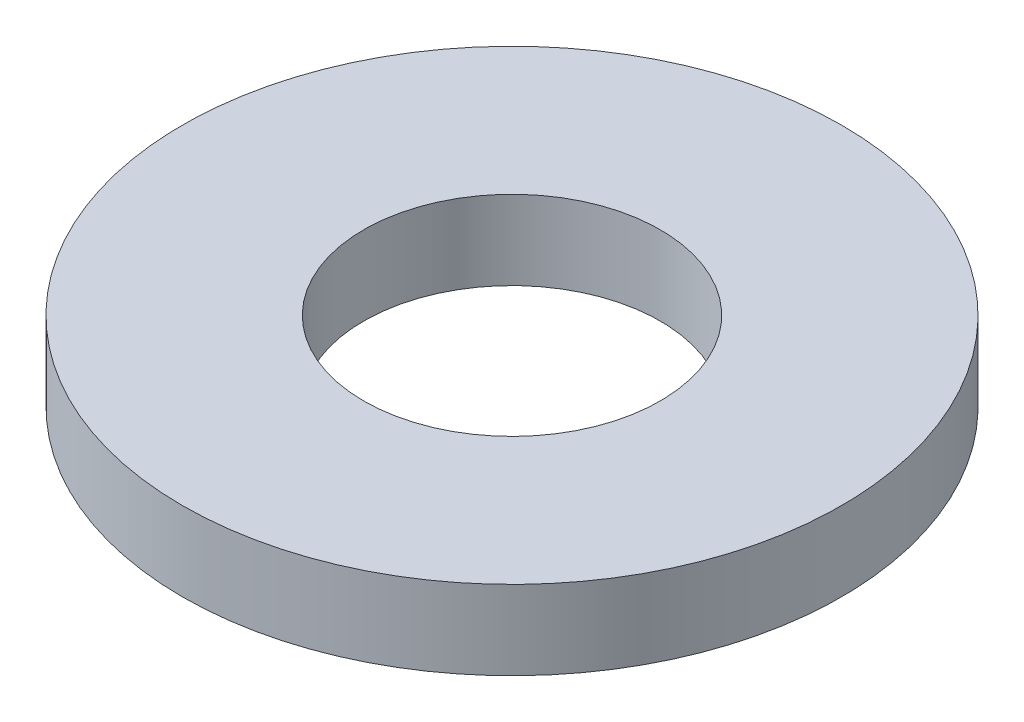
SolidWorks part; units mm, degrees
ref_plane "Front Plane" through (0, 0, 0) normal (0, 0, 1) x (1, 0, 0)
ref_plane "Top Plane" through (0, 0, 0) normal (0, 1, 0) x (1, 0, 0)
ref_plane "Right Plane" through (0, 0, 0) normal (1, 0, 0) x (0, 0, -1)
sketch "Sketch1" plane through (0, 0, 0) normal (0, 1, 0) x (1, 0, 0)
  circle A0 centre (0, 0) radius 100
  dimension "FLANGE_OD" = 200
extrude "Boss-Extrude1" add sketch "Sketch1" along normal blind 24
sketch "Sketch2" plane through (0, 0, 0) normal (0, 1, 0) x (1, 0, 0)
  circle A0 centre (0, 0) radius 45
  dimension "BORE_D" = 90
extrude "Cut-Extrude1" cut sketch "Sketch2" along normal through all
sketch "Sketch3" plane through (0, 24, 0) normal (0, 1, 0) x (1, 0, 0)
  circle A0 centre (0, 0) radius 33.4186 construction
  circle A1 centre (-33.4186, 0) radius 7.801
  dimension "BOLT_D" = 15.602
  dimension "BOLT_PCD" = 66.8372
extrude "Cut-Extrude2" cut sketch "Sketch3" against normal blind 22.6629 rebuild error yes
pattern_circular "CirPattern1" count 8 over 360 rebuild error yes
